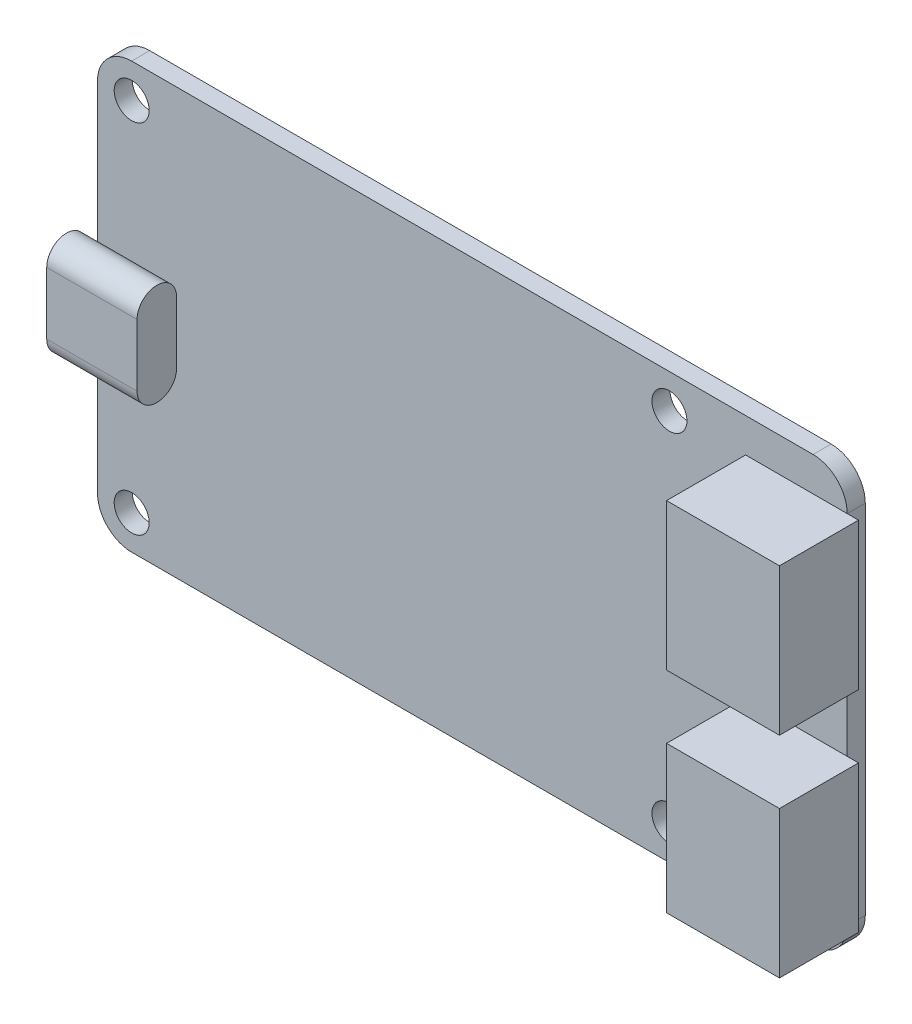
SolidWorks part; units mm, degrees
ref_plane "Plano frontal" through (0, 0, 0) normal (0, 0, 1) x (1, 0, 0)
ref_plane "Plano superior" through (0, 0, 0) normal (0, 1, 0) x (1, 0, 0)
ref_plane "Plano direito" through (0, 0, 0) normal (1, 0, 0) x (0, 0, -1)
sketch "Esboço1" plane through (0, 0, 0) normal (0, 0, 1) x (1, 0, 0)
  line L1 (-30.175, 18.835) -> (30.175, 18.835)
  line L2 (-33.2, 15.81) -> (-33.2, -15.81)
  line L3 (-30.175, -18.835) -> (30.175, -18.835)
  line L4 (33.2, 15.81) -> (33.2, -15.81)
  line L5 (-33.2, 18.835) -> (33.2, -18.835) construction
  line L6 (-33.2, -18.835) -> (33.2, 18.835) construction
  arc A0 (-33.2, -15.81) -> (-30.175, -18.835) centre (-30.175, -15.81) ccw
  arc A1 (30.175, -18.835) -> (33.2, -15.81) centre (30.175, -15.81) ccw
  arc A2 (30.175, 18.835) -> (33.2, 15.81) centre (30.175, 15.81) cw
  arc A3 (-30.175, 18.835) -> (-33.2, 15.81) centre (-30.175, 15.81) ccw
  circle A4 centre (-30.175, 15.81) radius 1.55
  circle A5 centre (-30.175, -15.81) radius 1.55
  circle A6 centre (17.455, 15.81) radius 1.55
  circle A7 centre (17.455, -15.81) radius 1.55
  point P0 (0, 0)
  point P24 (17.455, -15.81)
  point P25 (0, 0)
  point P26 (0, 0)
  dimension "D1" = 31.62
  dimension "D5" = 3.1
  dimension "D2" = 37.67
  dimension "D3" = 66.4
  dimension "D4" = 47.63
extrude "Ressalto-extrusão1" add sketch "Esboço1" along normal blind 1.6
sketch "Esboço2" plane through (0, 0, 1.6) normal (0, 0, 1) x (1, 0, 0)
  line L0 (0, 0) -> (18.5434, 0) construction
  line L1 (24.2, 15.81) -> (34.2, 15.81)
  line L2 (24.2, 15.81) -> (24.2, 2.81)
  line L3 (24.2, 2.81) -> (34.2, 2.81)
  line L4 (34.2, 15.81) -> (34.2, 2.81)
  line L5 (24.2, 15.81) -> (34.2, 2.81) construction
  line L6 (24.2, 2.81) -> (34.2, 15.81) construction
  line L7 (24.2, -2.81) -> (34.2, -15.81) construction
  line L8 (24.2, -15.81) -> (34.2, -2.81) construction
  line L9 (34.2, -15.81) -> (34.2, -2.81)
  line L10 (24.2, -2.81) -> (34.2, -2.81)
  line L11 (24.2, -15.81) -> (24.2, -2.81)
  line L12 (24.2, -15.81) -> (34.2, -15.81)
  line L13 (33.2, -15.81) -> (33.2, 15.81) construction
  point P0 (29.2, 9.31)
  point P12 (29.2, -9.31)
  dimension "D1" = 31.62
  dimension "D2" = 13
  dimension "D3" = 10
  dimension "D4" = 1
extrude "Ressalto-extrusão2" add sketch "Esboço2" along normal blind 7
sketch "Esboço3" plane through (-33.2, 0, 0) normal (-1, 0, 0) x (0, 0, 1)
  line L0 (3.35, 2.75) -> (3.35, -2.75) construction
  line L1 (5.1, 2.75) -> (5.1, -2.75)
  line L2 (1.6, 2.75) -> (1.6, -2.75)
  line L3 (0, 15.81) -> (0, -15.81) construction
  line L4 (1.6, 15.81) -> (1.6, -15.81) construction
  arc A0 (5.1, 2.75) -> (1.6, 2.75) centre (3.35, 2.75) ccw
  arc A1 (1.6, -2.75) -> (5.1, -2.75) centre (3.35, -2.75) ccw
  point P2 (3.35, 0)
  point P7 (0, 0)
  point P10 (0, 0)
  point P11 (1.6, -2.75)
  dimension "D1" = 1.75
  dimension "D2" = 9
extrude "Ressalto-extrusão3" add sketch "Esboço3" along normal blind 1 and the other way blind 7
